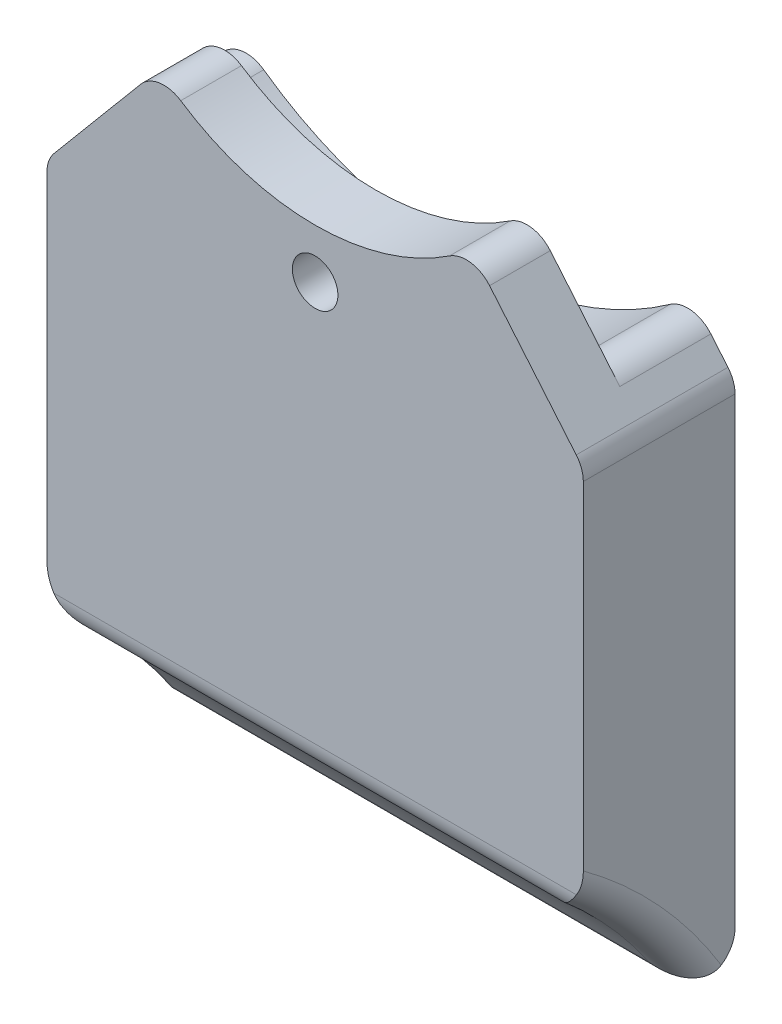
SolidWorks part; units mm, degrees
ref_plane "前视基准面" through (0, 0, 0) normal (0, 0, 1) x (1, 0, 0)
ref_plane "上视基准面" through (0, 0, 0) normal (0, 1, 0) x (1, 0, 0)
ref_plane "右视基准面" through (0, 0, 0) normal (1, 0, 0) x (0, 0, -1)
other "Configuration Table"
sketch "草图1" plane through (0, 0, 0) normal (0, 0, 1) x (1, 0, 0)
  line L0 (0, 0) -> (0, -23.1) construction
  line L1 (-10.2846, -12.2567) -> (-14.8484, -17.6956)
  line L2 (10.2846, -12.2567) -> (14.8484, -17.6956)
  circle A0 centre (0, -19.25) radius 1.5
  circle A1 centre (0, 0) radius 23.1
  circle A2 centre (0, 0) radius 16
  dimension "D1" = 3
  dimension "D3" = 46.2
  dimension "D4" = 32
  dimension "D2" = 19.25
  dimension "D5" = 80
extrude "凸台-拉伸1" add sketch "草图1" along normal blind 4 contours A2 L0 A0 A1 L2 | L0 A2 L1 A1 A0 region at (6.8502, -18.1582, 0) region at (-6.8502, -18.1582, 0)
sketch "草图3" plane through (0, 0, 4) normal (0, 0, 1) x (1, 0, 0)
  line L0 (-14.8484, -17.6956) -> (-17.6767, -21.0662)
  line L1 (14.8484, -17.6956) -> (17.6767, -21.0662)
  line L2 (-10.2846, -12.2567) -> (-14.8484, -17.6956)
  line L3 (14.8484, -17.6956) -> (10.2846, -12.2567)
  line L4 (-10.2846, -12.2567) -> (-14.8484, -17.6956)
  line L5 (14.8484, -17.6956) -> (10.2846, -12.2567)
  circle A0 centre (0, 0) radius 27.5
  arc A2 (-10.2846, -12.2567) -> (10.2846, -12.2567) centre (0, 0) ccw
  arc A3 (-14.8484, -17.6956) -> (14.8484, -17.6956) centre (0, 0) ccw
  arc A4 (-10.2846, -12.2567) -> (10.2846, -12.2567) centre (0, 0) ccw
  arc A5 (-14.8484, -17.6956) -> (14.8484, -17.6956) centre (0, 0) ccw
  arc M8 (-14.8484, -17.6956) -> (14.8484, -17.6956) centre (0, 0) ccw
  dimension "D2" = 55
  dimension "D1" = 0
extrude "凸台-拉伸2" add sketch "草图3" against normal blind 10 contours L0 A0 L1 M8 region at (0, -23.3531, 4)
sketch "草图4" plane through (0, 0, 4) normal (0, 0, 1) x (1, 0, 0)
  line L0 (-17.6767, -21.0662) -> (-17.6767, -71.0662)
  line L1 (-17.6767, -71.0662) -> (17.6767, -71.0662)
  line L2 (-10.2846, -12.2567) -> (-17.6767, -21.0662)
  line L3 (17.6767, -21.0662) -> (10.2846, -12.2567)
  line L4 (-10.2846, -12.2567) -> (-17.6767, -21.0662)
  line L5 (17.6767, -21.0662) -> (10.2846, -12.2567)
  line L6 (17.6767, -71.0662) -> (17.6767, -21.0662)
  arc A2 (-10.2846, -12.2567) -> (10.2846, -12.2567) centre (0, 0) ccw
  arc A3 (-17.6767, -21.0662) -> (17.6767, -21.0662) centre (0, 0) ccw
  arc A4 (-10.2846, -12.2567) -> (10.2846, -12.2567) centre (0, 0) ccw
  arc A5 (-17.6767, -21.0662) -> (17.6767, -21.0662) centre (0, 0) ccw
  arc M9 (-17.6767, -21.0662) -> (17.6767, -21.0662) centre (0, 0) ccw
  dimension "D2" = 50
  dimension "D1" = 0
extrude "凸台-拉伸3" add sketch "草图4" against normal blind 10 contours L1 L6 L0 M9 region at (0, -48.2279, 4)
sketch "草图7" plane through (17.6767, 0, 0) normal (1, 0, 0) x (0, 0, -1)
  line L3 (6, -71.0662) -> (6, -21.0662) construction
  line L6 (-4, -21.0662) -> (-4, -71.0662)
  line L7 (-4, -71.0662) -> (6, -71.0662)
  line L8 (6, -71.0662) -> (6, -21.0662)
  line L9 (6, -21.0662) -> (-4, -21.0662)
  line L10 (-4, -21.0662) -> (-4, -71.0662)
  line L11 (-4, -71.0662) -> (6, -71.0662)
  line L12 (6, -71.0662) -> (6, -21.0662)
  line L13 (6, -21.0662) -> (-4, -21.0662)
  arc A1 (-4, -46.5486) -> (6, -60.3033) centre (-24.6678, -72.0871) cw
  ellipse E0 centre (-25.5146, -65.2388) end of major axis (-25.5146, -36.7388) minor radius 28.4985 (-26.7681, -93.7112) -> (-24.261, -36.7664) ccw construction
  line M6 (-4, -71.0662) -> (6, -71.0662)
  line M7 (6, -71.0662) -> (6, -21.0662)
  dimension "D1" = 0
extrude "切除-拉伸1" cut sketch "草图7" against normal through all contours L10 M6 M7 region at (17.6767, -61.2177, -0.4184)
fillet "圆角1" radius 2 10 edges at (14.8484, -17.6956, -3) (-14.8484, -17.6956, -3) (-17.6767, -21.0662, -1) (10.2846, -12.2567, 2) (17.6767, -21.0662, -1) (-10.2846, -12.2567, 2) (0, -60.3033, -6) (-17.6767, -52.7677, -1.9054) (0, -46.5486, 4) (17.6767, -52.7677, -1.9054)
